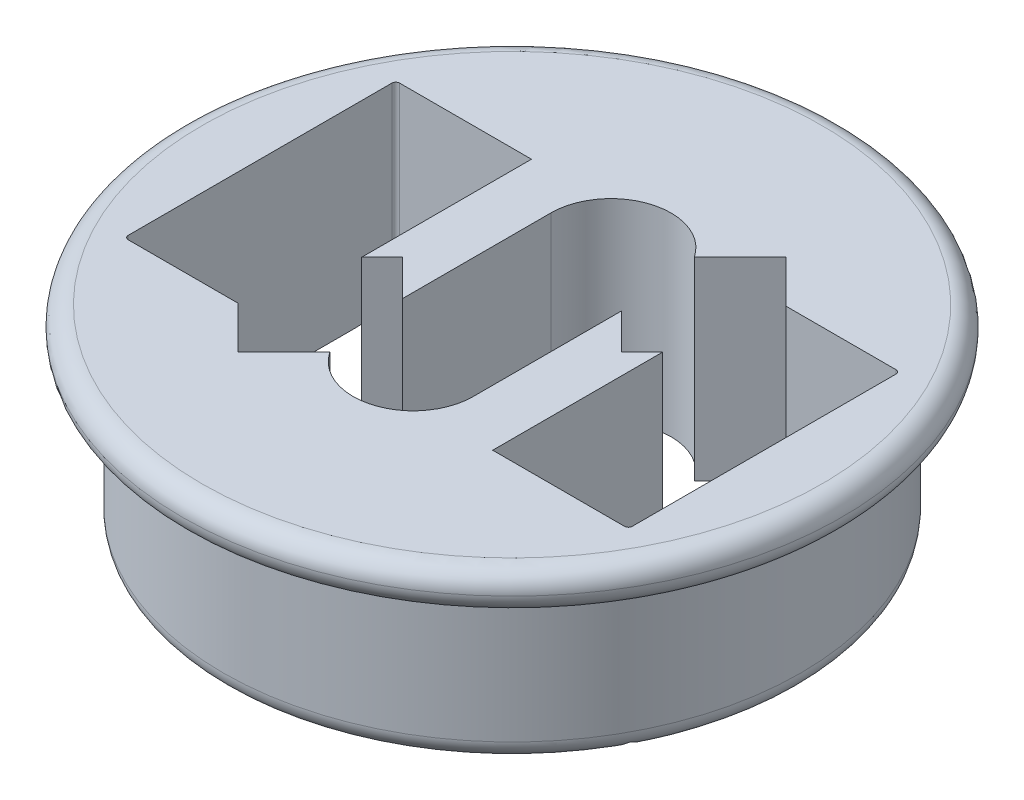
SolidWorks part; units mm, degrees
ref_plane "Front Plane" through (0, 0, 0) normal (0, 0, 1) x (1, 0, 0)
ref_plane "Top Plane" through (0, 0, 0) normal (0, 1, 0) x (1, 0, 0)
ref_plane "Right Plane" through (0, 0, 0) normal (1, 0, 0) x (0, 0, -1)
sketch "Sketch1" plane through (0, 0, 0) normal (0, 1, 0) x (1, 0, 0)
  circle A0 centre (0, 0) radius 7.45
extrude "Boss-Extrude1" add sketch "Sketch1" along normal blind 4 contours A0
sketch "Sketch2" plane through (0, 4, 0) normal (0, 1, 0) x (1, 0, 0)
  circle A0 centre (0, 0) radius 8.5
extrude "Boss-Extrude2" add sketch "Sketch2" along normal blind 1
sketch "Sketch3" plane through (0, 5, 0) normal (0, 1, 0) x (1, 0, 0)
  line L0 (0, -8.5) -> (0, 8.5) construction
  line L1 (-8.5, 0) -> (8.5, 0) construction
  line L2 (-2.2959, -1.15) -> (-2.2959, 1.15) construction
  line L3 (-2.2959, -3.5) -> (-2.2959, 3.5) construction
  line L4 (-5, 4.395) -> (5, 4.395) construction
  line L5 (-7, 4.395) -> (7, 4.395) construction
  line L6 (-2.7113, 1.15) -> (-2.7113, 3.5) construction
  line L7 (-2.7113, -1.15) -> (-2.7113, -3.5) construction
  line L8 (-6.5, 3.914) -> (-3, 3.914) construction
  line L9 (5, 3.914) -> (7, 3.914) construction
  line L10 (-6.5, 3.5) -> (-6.5, 0)
  line L11 (-6.5, 0) -> (-3, 0)
  line L12 (-3, 0) -> (-3, 3.5)
  line L13 (-3, 3.5) -> (-6.5, 3.5)
  line L14 (-6.5, 0) -> (-6.5, -3.5)
  line L15 (-6.5, -3.5) -> (-3, -3.5)
  line L16 (-3, -3.5) -> (-3, 0)
  line L17 (-6.5, 0) -> (-3, 0)
  line L18 (3, -3.5) -> (3, 0)
  line L19 (6.5, -3.5) -> (3, -3.5)
  line L20 (6.5, 0) -> (6.5, -3.5)
  line L21 (6.5, 0) -> (3, 0)
  line L22 (6.5, 3.5) -> (6.5, 0)
  line L23 (6.5, 0) -> (3, 0)
  line L24 (3, 0) -> (3, 3.5)
  line L25 (3, 3.5) -> (6.5, 3.5)
  line L26 (0, -2.55) -> (0, 2.55) construction
  line L27 (-1.55, -2.55) -> (-1.55, 2.55)
  line L28 (1.55, -2.55) -> (1.55, 2.55)
  line L29 (-1.4142, -1.4142) -> (1.4142, 1.4142) construction
  line L30 (-3.5355, -3.5355) -> (3.5355, 3.5355) construction
  line L31 (2.4749, 4.5962) -> (4.5962, 2.4749) construction
  line L32 (0.3536, 2.4749) -> (2.4749, 0.3536) construction
  line L33 (0.3536, 2.4749) -> (2.4749, 4.5962)
  line L34 (2.4749, 4.5962) -> (4.5962, 2.4749)
  line L35 (4.5962, 2.4749) -> (2.4749, 0.3536)
  line L36 (2.4749, 0.3536) -> (0.3536, 2.4749)
  line L37 (-6.0104, 6.0104) -> (6.0104, -6.0104) construction
  line L38 (-4.5962, -2.4749) -> (-2.4749, -4.5962)
  line L39 (-2.4749, -0.3536) -> (-4.5962, -2.4749)
  line L40 (-2.4749, -4.5962) -> (-0.3536, -2.4749)
  line L41 (-0.3536, -2.4749) -> (-2.4749, -0.3536)
  circle A0 centre (0, 0) radius 8.5 construction
  arc A1 (-1.55, -2.55) -> (1.55, -2.55) centre (0, -2.55) ccw
  arc A2 (1.55, 2.55) -> (-1.55, 2.55) centre (0, 2.55) ccw
  point P7 (0, 0)
  point P11 (0, 0)
  point P14 (-2.2959, 0)
  point P17 (-2.2959, 0)
  point P20 (0, 4.395)
  point P23 (0, 4.395)
  point P48 (0, 0)
  point P56 (0, 0)
  point P59 (0, 0)
  point P62 (3.5355, 3.5355)
  point P65 (1.4142, 1.4142)
  point P68 (0, 0)
  point P72 (0, 0)
  point P73 (0, 0)
  point P74 (0, 0)
  point P75 (0, 0)
  point P76 (0, 0)
  point P77 (0, 0)
  point P78 (0, 0)
  dimension "D1" = 3.5
  dimension "D2" = 3.5
  dimension "D3" = 5.1
  dimension "D4" = 3.1
  dimension "D5" = 3
  dimension "D6" = 3
extrude "Cut-Extrude1" cut sketch "Sketch3" against normal through all contours L18 L21 L20 L19 | L25 L22 L23 L24 | L16 L17 L14 L15 | L13 L10 L11 L12
extrude "Cut-Extrude2" cut sketch "Sketch3<4>" against normal through all contours L28 A2 L27 A1
sketch "Sketch3<4>" plane through (0, 5, 0) normal (0, 1, 0) x (1, 0, 0) same geometry as "Sketch3"
extrude "Cut-Extrude3" cut sketch "Sketch3<5>" against normal through all contours A2 L28 L36 L35 L34 L33 | A1 L27 L41 L39 L38 L40 region at (-2.3258, 5, 2.5288) region at (2.3258, 5, -2.5288)
sketch "Sketch3<5>" plane through (0, 5, 0) normal (0, 1, 0) x (1, 0, 0) same geometry as "Sketch3"
fillet "Fillet3" radius 0.5 3 edges at (0, 0, 7.45) (0, 4, 8.5) (0, 5, 8.5)
fillet "Fillet5" radius 0.1 4 edges at (-6.5, 2.6245, 3.5) (-6.5, 2.6245, -3.5) (6.5, 2.6245, 3.5) (6.5, 2.6245, -3.5)
